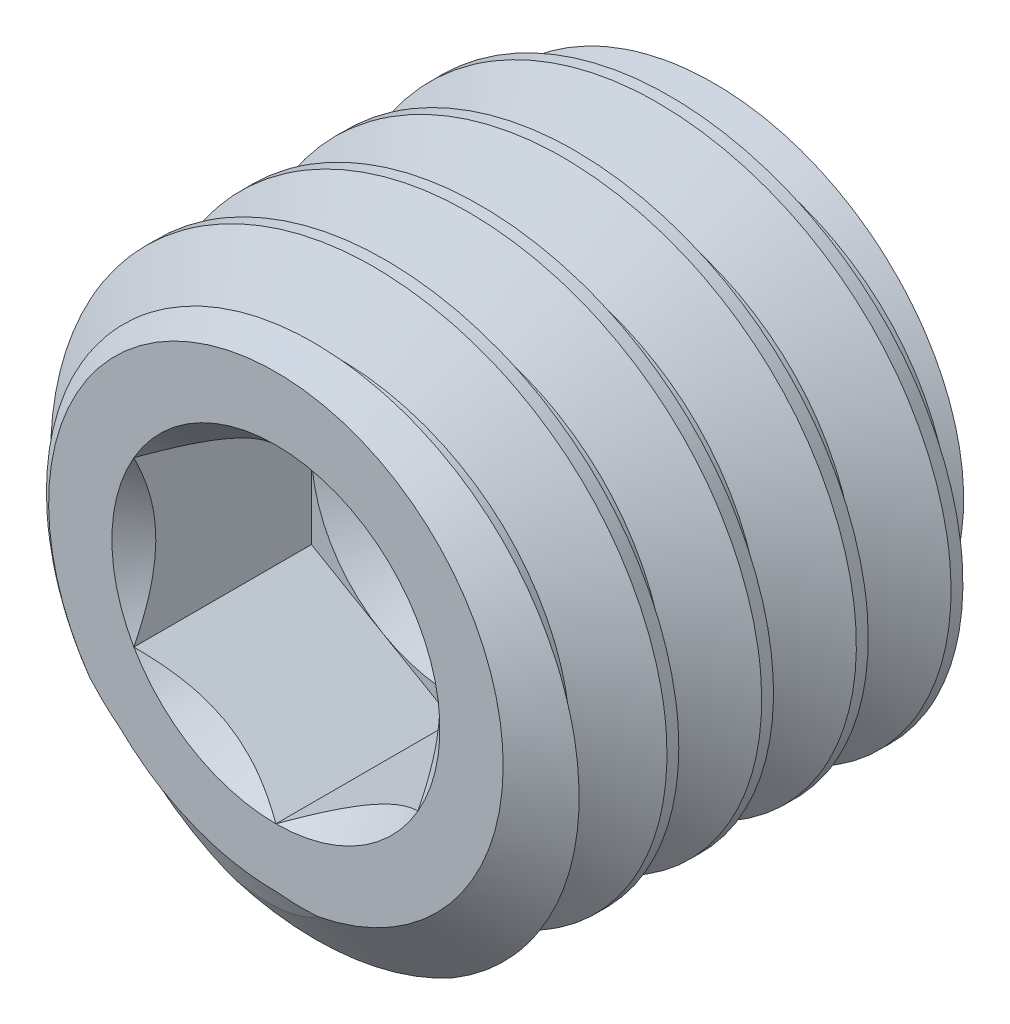
SolidWorks part; units mm, degrees
ref_plane "Front" through (0, 0, 0) normal (0, 0, 1) x (1, 0, 0)
ref_plane "Top" through (0, 0, 0) normal (0, 1, 0) x (1, 0, 0)
ref_plane "Right" through (0, 0, 0) normal (1, 0, 0) x (0, 0, -1)
sketch "Body Sketch" plane through (0, 0, 0) normal (1, 0, 0) x (0, 0, -1)
  line L0 (-1.5, 0) -> (-1.5, 1.2)
  line L1 (-1.5, 1.2) -> (-1.2899, 1.5)
  line L2 (-1.2899, 1.5) -> (0.7466, 1.5)
  line L3 (0.7466, 1.5) -> (1.5, 0.195)
  line L4 (-1.5, 1.2) -> (-1.5, -1.2) construction
  line L5 (1.5, 0) -> (-1.5, 0)
  line L6 (0, 1.5) -> (0, -1.5) construction
  line L8 (1.5, 0.195) -> (1.5, 0)
  line L9 (-1.5, -1.5) -> (1.5, -1.5) construction
  line L10 (1.5, 0.195) -> (1.5, -0.195) construction
  line L11 (1.5, -0.195) -> (0.7466, -1.5) construction
  line L13 (1.5, 0.195) -> (1.3874, 0) construction
  line L15 (1.3874, 0) -> (1.5, -0.195) construction
  dimension "D3" = 35
  dimension "D7" = 2.4
  dimension "Diameter" = 3
  dimension "Length" = 3
  dimension "D2" = 0.39
  dimension "Cone Angle" = 120
  dimension "D90" = 120
revolve "Body Revolve" add sketch "Body Sketch" angle 360 about L5
ref_plane "Tip Plane" through (0, 0, -1.5) normal (0, 0, 1) x (1, 0, 0)
sketch "Spiral Sketch" plane through (0, 0, -1.5) normal (0, 0, 1) x (1, 0, 0)
  circle A0 centre (0, 0) radius 1.5 construction
  circle A1 centre (0, 0) radius 1.5
sketch "Hex Sketch" plane through (0, 0, 1.5) normal (0, 0, 1) x (1, 0, 0)
  line L1 (0, 0.866) -> (-0.75, 0.433)
  line L2 (-0.75, 0.433) -> (-0.75, -0.433)
  line L3 (-0.75, -0.433) -> (0, -0.866)
  line L4 (0, -0.866) -> (0.75, -0.433)
  line L5 (0.75, -0.433) -> (0.75, 0.433)
  line L6 (0.75, 0.433) -> (0, 0.866)
  circle A0 centre (0, 0) radius 0.75 construction
  dimension "Hex" = 1.5
extrude "Hex Extrude" cut sketch "Hex Sketch" against normal blind 0.9375
sketch "Hex Entry Sketch" plane through (0, 0, 1.5) normal (0, 0, 1) x (1, 0, 0)
  circle A0 centre (0, 0) radius 0.866
extrude "Hex Entry Extrude" cut sketch "Hex Entry Sketch" against normal through all draft 45
sketch "Hex Bottom Sketch" plane through (0, 0, 0.5625) normal (0, 0, 1) x (1, 0, 0)
  circle A0 centre (0, 0) radius 0.75 construction
  circle A1 centre (0, 0) radius 0.75
extrude "Hex Bottom Extrude" cut sketch "Hex Bottom Sketch" against normal through all draft 60
curve "Helix/Spiral" pitch 0.5 height 3.5 radius 1.5 centre (0, 0, -1.5) axis (0, 0, 1) start towards (0, 1, 0)
sketch "Sketch28" plane through (0, 0, 0) normal (1, 0, 0) x (0, 0, -1)
  line L0 (1.5, 1.5) -> (1.9375, 1.5)
  line L1 (1.9375, 1.5) -> (1.75, 1.1752)
  line L2 (1.75, 1.1752) -> (1.6875, 1.1752)
  line L3 (1.6875, 1.1752) -> (1.5, 1.5)
  line L4 (1.5937, 1.3376) -> (1.8437, 1.3376) construction
  line L6 (-1.2899, 1.5) -> (0.7466, 1.5) construction
  line L7 (1.5, 6.7518) -> (1.5, -6.7518) construction
  dimension "D1" = 0.0625
  dimension "D3" = 60
  dimension "D2" = 0.25
sweep "Thread Sweep" cut profiles "Sketch28" path "Helix/Spiral"
ref_plane "Contact Plane 1" through (0, 0, 1.5) normal (0, 0, 1) x (1, 0, 0)
ref_plane "Contact Plane 2" through (0, 0, -1.5) normal (0, 0, -1) x (-1, 0, 0)
ref_axis "Center Axis 1" through (0, 0, 49.8835) along (0, 0, -1)
equation "\"D7@Body Sketch\" = \"Diameter@Body Sketch\" * .8"
equation "\"D1@Sketch28\" = \"D4@Helix/Spiral\" * .125"
equation "\"D3@Helix/Spiral\" = \"Length@Body Sketch\" + \"D4@Helix/Spiral\""
equation "\"hex Depth@Hex Extrude\" = \"Hex@Hex Sketch\" * .625"
equation "\"D2@Sketch28\" = \"D4@Helix/Spiral\" * .5"
equation "\"D2@Body Sketch\" = \"Diameter@Body Sketch\" * .13"
equation "\"D90@Body Sketch\" = \"Cone Angle@Body Sketch\""
equation "\"Diameter\"= 3mm"
equation "\"Thread Pitch\"= 0.5mm"
equation "\"Hex Size\"= 1.5mm"
equation "\"Diameter@Body Sketch\" = \"Diameter\""
equation "\"Hex@Hex Sketch\" = \"Hex Size\""
equation "\"D4@Helix/Spiral\"=\"Thread Pitch\""
